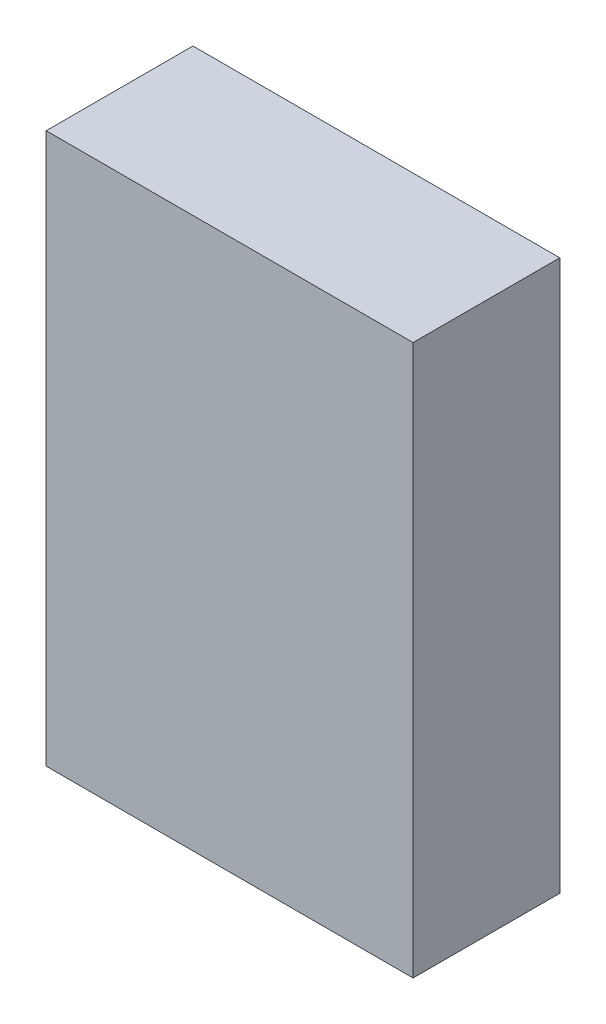
SolidWorks part; units mm, degrees
ref_plane "Plan de face" through (0, 0, 0) normal (0, 0, 1) x (1, 0, 0)
ref_plane "Plan de dessus" through (0, 0, 0) normal (0, 1, 0) x (1, 0, 0)
ref_plane "Plan de droite" through (0, 0, 0) normal (1, 0, 0) x (0, 0, -1)
sketch "Esquisse1" plane through (0, 0, 0) normal (0, 0, 1) x (1, 0, 0)
  line L1 (-56.626, 31.2883) -> (143.374, 31.2883)
  line L2 (-56.626, 31.2883) -> (-56.626, -268.7117)
  line L3 (-56.626, -268.7117) -> (143.374, -268.7117)
  line L4 (143.374, 31.2883) -> (143.374, -268.7117)
  dimension "D1" = 200
  dimension "D2" = 300
extrude "Boss.-Extru.1" add sketch "Esquisse1" along normal blind 80
shell "Coque1" thickness 4 removed face at (43.374, -118.7117, 0)
sketch "Esquisse3" plane through (0, 0, 0) normal (0, 0, -1) x (-1, 0, 0)
  line L8 (54.726, -266.8117) -> (54.726, 29.3883)
  line L9 (54.726, 29.3883) -> (-141.474, 29.3883)
  line L10 (-141.474, 29.3883) -> (-141.474, -266.8117)
  line L11 (-141.474, -266.8117) -> (54.726, -266.8117)
  line L12 (54.726, -266.8117) -> (54.726, 29.3883)
  line L13 (54.726, 29.3883) -> (-141.474, 29.3883)
  line L14 (-141.474, 29.3883) -> (-141.474, -266.8117)
  line L15 (-141.474, -266.8117) -> (54.726, -266.8117)
  dimension "D1" = 1.9
extrude "Enlèv. mat.-Extru.2" cut sketch "Esquisse3" against normal blind 4.1
sketch "Esquisse4" plane through (0, 0, 76) normal (0, 0, -1) x (-1, 0, 0)
  line L0 (2.626, -174.7117) -> (52.626, -174.7117)
  line L1 (52.626, 27.2883) -> (52.626, -264.7117) construction
  line L2 (2.626, -174.7117) -> (2.626, -264.7117)
  line L3 (52.626, -264.7117) -> (-139.374, -264.7117) construction
  line L4 (-89.374, -174.7117) -> (-139.374, -174.7117)
  line L5 (-89.374, -174.7117) -> (-89.374, -264.7117)
  line L6 (-139.374, -264.7117) -> (-139.374, 27.2883) construction
  line L8 (-89.374, -62.7117) -> (-139.374, -62.7117)
  line L9 (-89.374, -62.7117) -> (-89.374, 27.2883)
  line L10 (-139.374, 27.2883) -> (52.626, 27.2883) construction
  line L11 (2.626, -62.7117) -> (52.626, -62.7117)
  line L12 (2.626, -62.7117) -> (2.626, 27.2883)
  line L13 (-119.374, 7.2883) -> (-119.374, 27.2883)
  line L14 (-119.374, 27.2883) -> (-119.374, 7.2883)
  line L15 (-119.374, 7.2883) -> (-139.374, 7.2883)
  circle A0 centre (2.626, -174.7117) radius 9
  circle A1 centre (-89.374, -174.7117) radius 9
  circle A2 centre (2.626, -62.7117) radius 9
  circle A3 centre (-89.374, -62.7117) radius 9
  circle A4 centre (-119.374, 7.2883) radius 9
  dimension "D1" = 50
  dimension "D2" = 90
  dimension "D3" = 50
  dimension "D4" = 90
  dimension "D5" = 90
  dimension "D6" = 90
  dimension "D7" = 50
  dimension "D8" = 50
  dimension "D9" = 20
  dimension "D10" = 20
extrude "Boss.-Extru.2" add sketch "Esquisse4" along normal blind 67.9 contours A4
sketch "Esquisse5" plane through (0, 0, 8.1) normal (0, 0, -1) x (-1, 0, 0)
  circle A3 centre (-119.374, 7.2883) radius 2.5
  circle A4 centre (-119.374, 7.2883) radius 2.5
  dimension "D1" = 6.5
extrude "Enlèv. mat.-Extru.3" cut sketch "Esquisse5" against normal blind 30
extrude "Boss.-Extru.3" add sketch "Esquisse4<4>" along normal blind 15 contours L9 A3 L8 | L8 A3 L9 | L2 A0 L0 | L0 A0 L2 | A2 | A1 region at (-1.3528, -173.4384, 76) region at (-6.4458, -178.5314, 76) region at (88.1007, -63.9849, 76) region at (93.1937, -58.8919, 76)
sketch "Esquisse4<4>" plane through (0, 0, 76) normal (0, 0, -1) x (-1, 0, 0) same geometry as "Esquisse4"
sketch "Esquisse6" plane through (0, 0, 61) normal (0, 0, -1) x (-1, 0, 0)
  circle A3 centre (-89.374, -62.7117) radius 2.5
  circle A4 centre (-89.374, -62.7117) radius 2.5
  circle A6 centre (2.626, -62.7117) radius 2.5
  circle A7 centre (2.626, -62.7117) radius 2.5
  circle A9 centre (-89.374, -174.7117) radius 2.5
  circle A10 centre (-89.374, -174.7117) radius 2.5
  circle A12 centre (2.626, -174.7117) radius 2.5
  circle A13 centre (2.626, -174.7117) radius 2.5
  dimension "D1" = 6.5
  dimension "D2" = 6.5
  dimension "D3" = 6.5
  dimension "D4" = 6.5
extrude "Enlèv. mat.-Extru.6" cut sketch "Esquisse6" against normal blind 10
sketch "Esquisse8" plane through (0, 0, 76) normal (0, 0, -1) x (-1, 0, 0)
  line L0 (32.626, 7.2883) -> (52.626, 7.2883)
  line L1 (52.626, 27.2883) -> (52.626, -264.7117) construction
  line L2 (32.626, 7.2883) -> (32.626, 27.2883)
  line L3 (-139.374, 27.2883) -> (52.626, 27.2883) construction
  line L4 (32.626, -244.7117) -> (52.626, -244.7117)
  line L5 (32.626, -244.7117) -> (32.626, -264.7117)
  line L6 (52.626, -264.7117) -> (-139.374, -264.7117) construction
  line L7 (-119.374, -244.7117) -> (-139.374, -244.7117)
  line L8 (-139.374, -264.7117) -> (-139.374, 27.2883) construction
  line L9 (-119.374, -244.7117) -> (-119.374, -264.7117)
  circle A0 centre (32.626, 7.2883) radius 9
  circle A1 centre (32.626, -244.7117) radius 9
  circle A2 centre (-119.374, -244.7117) radius 9
  dimension "D1" = 20
  dimension "D2" = 20
  dimension "D3" = 20
  dimension "D4" = 20
  dimension "D5" = 20
  dimension "D6" = 20
extrude "Boss.-Extru.5" add sketch "Esquisse8" along normal blind 68 contours L0 A0 L2 | L2 A0 L0 | L5 A1 L4 | L4 A1 L5 | A2 region at (-36.4458, 11.1081, 76) region at (-31.3528, 6.0151, 76) region at (-31.3528, -243.4384, 76) region at (-36.4458, -248.5314, 76)
sketch "Esquisse9" plane through (0, 0, 8) normal (0, 0, -1) x (-1, 0, 0)
  circle A2 centre (32.626, 7.2883) radius 2.5
  circle A3 centre (32.626, 7.2883) radius 2.5
  circle A4 centre (32.626, -244.7117) radius 2.5
  circle A5 centre (32.626, -244.7117) radius 2.5
  circle A7 centre (-119.374, -244.7117) radius 2.5
  circle A8 centre (-119.374, -244.7117) radius 2.5
  dimension "D1" = 6.5
  dimension "D2" = 6.5
  dimension "D3" = 6.5
extrude "Enlèv. mat.-Extru.8" cut sketch "Esquisse9" against normal blind 30 contours A8 | A5 | A3
